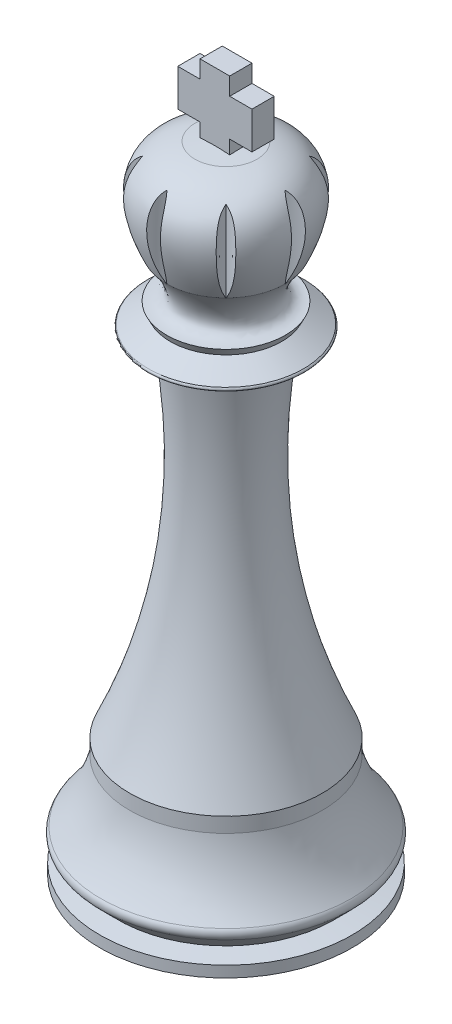
SolidWorks part; units mm, degrees
material "Maple"
ref_plane "Front Plane" through (0, 0, 0) normal (0, 0, 1) x (1, 0, 0)
ref_plane "Top Plane" through (0, 0, 0) normal (0, 1, 0) x (1, 0, 0)
ref_plane "Right Plane" through (0, 0, 0) normal (1, 0, 0) x (0, 0, -1)
sketch "Sketch2" plane through (0, 0, 0) normal (0, 0, 1) x (1, 0, 0)
  line L0 (0, 0) -> (17, 0)
  line L1 (0, 0) -> (0, 95) construction
  line L2 (17, 0) -> (17, 1.5)
  line L3 (17, 1.5) -> (14.4497, 1.9497)
  line L4 (14.4497, 1.9497) -> (17.5, 5)
  line L5 (12.9764, 16.03) -> (12.9764, 14.03)
  line L6 (-0.0236, 14.03) -> (12.9764, 14.03) construction
  line L7 (7, 63) -> (-0.0236, 63) construction
  line L8 (0, 95) -> (0, 0) construction
  line L9 (11, 64) -> (7, 63)
  line L10 (8, 67) -> (7.5, 66)
  line L11 (7.5, 66) -> (11, 64)
  line L12 (-0.0236, 66) -> (11, 66) construction
  line L13 (11, 66) -> (11, 63) construction
  line L14 (7, 63) -> (11, 63) construction
  line L15 (0, 86) -> (0, 0)
  line L17 (0, 86) -> (11, 86) construction
  line L18 (11, 86) -> (11, 63) construction
  line L20 (8, 73) -> (8, 67) construction
  line L21 (0, 86) -> (4.1886, 85.6335)
  spline S0 degree 3 poles (8, 67) (3.868, 67.0315) (6.6706, 71.4192) (8, 73) knots 0 0 0 0 1 1 1 1
  spline S1 degree 2 poles (12.9764, 14.03) (13.9021, 8.7376) (17.5, 5) knots 0 0 0 1 1 1
  spline S2 degree 2 poles (7, 63) (3.049, 38.1074) (12.9764, 16.03) knots 0 0 0 1 1 1
  spline S3 degree 2 poles (4.1886, 85.6335) (12.9981, 83.6223) (8, 73) knots 0 0 0 1 1 1
  dimension "D1" = 17
  dimension "D2" = 1.5
  dimension "D4" = 55
  dimension "D5" = 5
  dimension "D6" = 100
  dimension "D7" = 13
  dimension "D8" = 3
  dimension "D9" = 1
  dimension "D10" = 1
  dimension "D11" = 95
  dimension "D12" = 14.03
  dimension "D13" = 2
  dimension "D14" = 63
  dimension "D18" = 11
  dimension "D15" = 6
  dimension "D16" = 86
  dimension "D17" = 8
  dimension "D19" = 5
revolve "Revolve1" add sketch "Sketch2" angle 360 about L8
fillet "Fillet1" radius 1 1 edges at (-17.5, 5, 0)
fillet "Fillet2" radius 0.25 1 edges at (-11, 64, 0)
sketch "Sketch3" plane through (0, 0, 0) normal (0, 0, 1) x (1, 0, 0)
  line L0 (0, 0) -> (0, 95) construction
  line L1 (0, 85.6335) -> (5, 85.6335) construction
  line L2 (-4.1886, 85.6335) -> (4.1886, 85.6335) construction
  line L3 (-2, 95) -> (2, 95)
  line L4 (2, 95) -> (2, 92.6335)
  line L5 (2, 92.6335) -> (5, 92.6335)
  line L6 (5, 92.6335) -> (5, 87.6335)
  line L7 (5, 87.6335) -> (2, 87.6335)
  line L8 (2, 87.6335) -> (2, 85.6335)
  line L9 (2, 85.6335) -> (-2, 85.6335)
  line L10 (-2, 87.6335) -> (-2, 85.6335)
  line L11 (-5, 87.6335) -> (-2, 87.6335)
  line L12 (-5, 92.6335) -> (-5, 87.6335)
  line L13 (-2, 92.6335) -> (-5, 92.6335)
  line L14 (-2, 95) -> (-2, 92.6335)
  dimension "D1" = 95
  dimension "D2" = 5
  dimension "D3" = 5
  dimension "D4" = 2
  dimension "D5" = 2
extrude "Boss-Extrude1" add sketch "Sketch3" along normal mid plane 3
sketch "Sketch4" plane through (0, 95, 0) normal (0, 1, 0) x (1, 0, 0)
  line L0 (0, 0) -> (0, 17.7712) construction
  line L1 (-1, 10.5384) -> (1, 10.5384)
  circle A0 centre (0, 0) radius 10.5858 construction
  spline S0 degree 2 poles (-1, 10.5384) (-1.0233, 9.0967) (0, 7.9549) knots 0 0 0 1 1 1
  spline S1 degree 2 poles (1, 10.5384) (1.0233, 9.0967) (0, 7.9549) knots 0 0 0 1 1 1
  point P8 (0, 10.5384)
  dimension "D1" = 2
extrude "Cut-Extrude1" cut sketch "Sketch4" against normal up to surface (30.7633 mm away) up to face at (-10.4598, 64.3087, 0)
pattern_circular "CirPattern1" count 8 over 360 about axis through (0, 5.6861, 0) along (0, 1, 0) of "Cut-Extrude1"
equation "\"height\"= 95mm"
equation "\"baseRadius\"= 17mm"
equation "\"D1@Sketch2\"=\"baseRadius\""
equation "\"D7@Sketch2\"=\"baseRadius\"-4"
equation "\"D11@Sketch2\"=\"height\""
equation "\"D1@Sketch3\"=\"height\""
